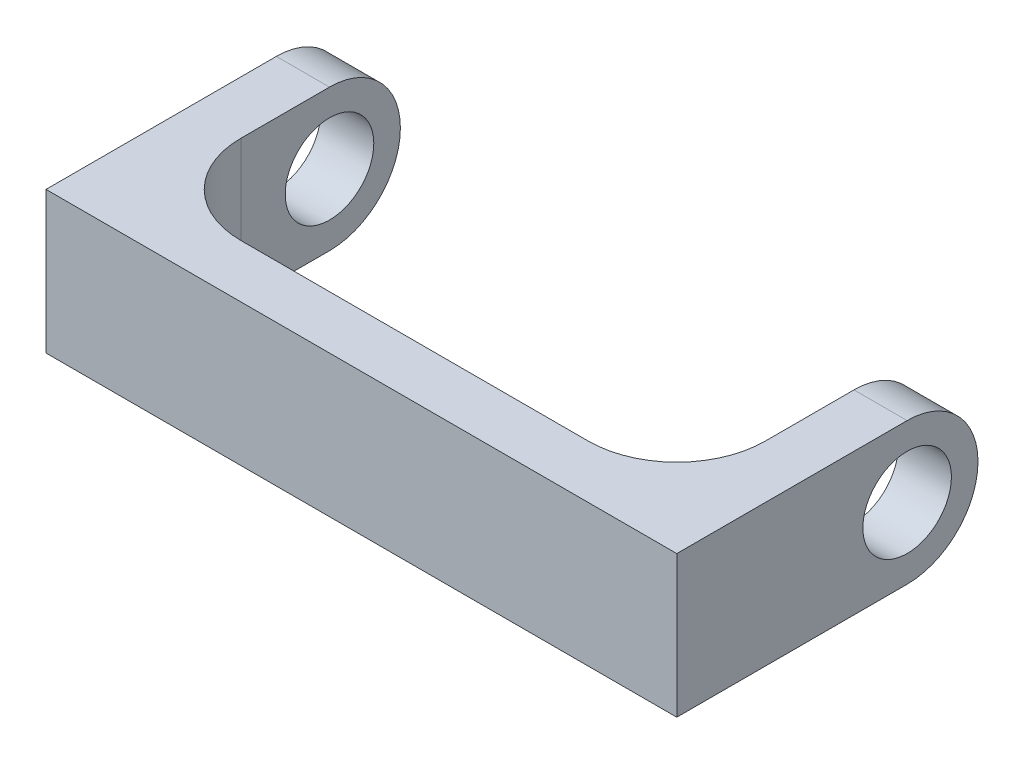
SolidWorks part; units mm, degrees
note: The reader was unsure of these and kept them because the rebuilt part matched: shared geometry of "Sketch2<3>", "Sketch2<4>".
material "5052-H32"
ref_plane "Front Plane" through (0, 0, 0) normal (0, 0, 1) x (1, 0, 0)
ref_plane "Top Plane" through (0, 0, 0) normal (0, 1, 0) x (1, 0, 0)
ref_plane "Right Plane" through (0, 0, 0) normal (1, 0, 0) x (0, 0, -1)
sketch "Sketch2" plane through (0, 0, 0) normal (1, 0, 0) x (0, 0, -1)
  line L0 (-10, 4) -> (0, 4) construction
  line L1 (0, -4) -> (-10, -4) construction
  line L2 (-10, 4) -> (-10, -4) construction
  line L3 (-10, 4) -> (0, 4)
  line L4 (0, -4) -> (-10, -4)
  line L5 (-10, 4) -> (-10, -4)
  line L6 (-10, 4) -> (-13, 4)
  line L7 (-13, 4) -> (-13, -4)
  line L8 (-13, -4) -> (-10, -4)
  arc A0 (0, -4) -> (0, 4) centre (0, 0) ccw construction
  circle A1 centre (0, 0) radius 2.5 construction
  arc A2 (0, -4) -> (0, 4) centre (0, 0) ccw
  circle A3 centre (0, 0) radius 2.5
extrude "Boss-Extrude1" add sketch "Sketch2" along normal up to vertex (2.5 mm away) from vertex at -0.5 contours L7 L8 L5 L6 | L4 A2 L3 L5 A3
extrude "Boss-Extrude2" add sketch "Sketch2<3>" along normal up to vertex (32.1 mm away) from vertex at 2.5 contours L7 L8 L5 L6
sketch "Sketch2<3>" plane through (0, 0, 0) normal (1, 0, 0) x (0, 0, -1) same geometry as "Sketch2"
extrude "Boss-Extrude3" add sketch "Sketch2<4>" along normal up to vertex (35.1 mm away) from vertex at 32.1 contours L7 L8 L5 L6 | L4 A2 L3 L5 A3
sketch "Sketch2<4>" plane through (0, 0, 0) normal (1, 0, 0) x (0, 0, -1) same geometry as "Sketch2"
fillet "Fillet1" radius 5 2 edges at (32.1, 0, 10) (2.5, 0, 10)
